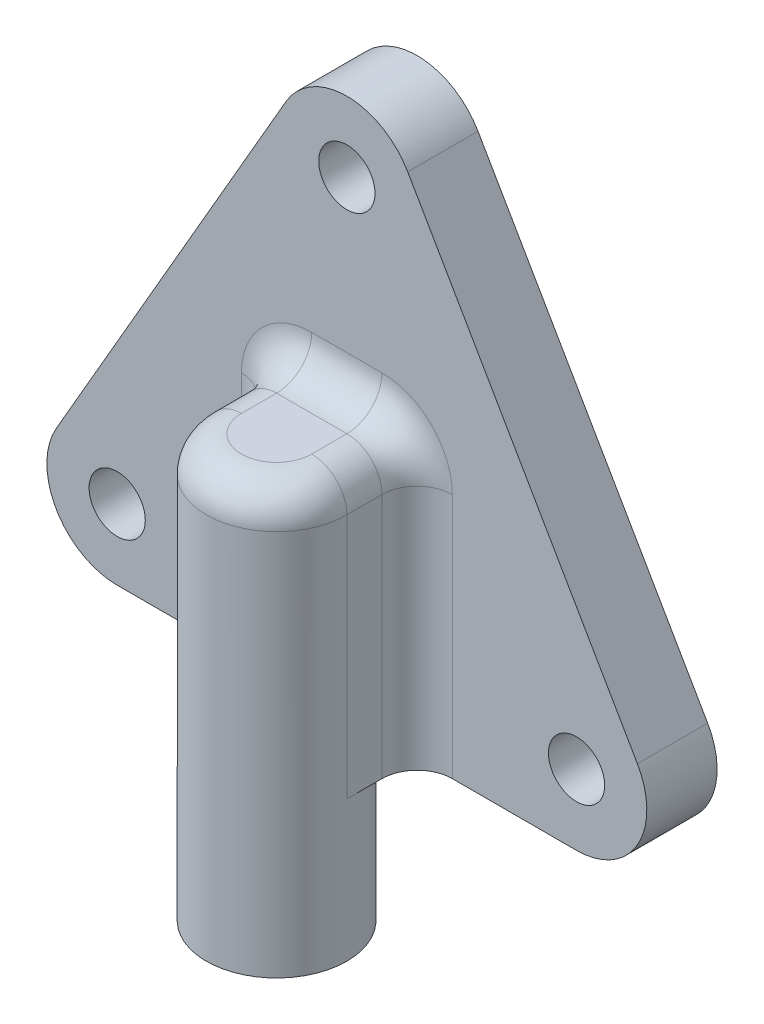
SolidWorks part; units mm, degrees
note: The reader was unsure of these and kept them because the rebuilt part matched: shared geometry of "Schizzo2<3>".
ref_plane "Piano frontale" through (0, 0, 0) normal (0, 0, 1) x (1, 0, 0)
ref_plane "Piano superiore" through (0, 0, 0) normal (0, 1, 0) x (1, 0, 0)
ref_plane "Piano destro" through (0, 0, 0) normal (1, 0, 0) x (0, 0, -1)
sketch "Schizzo1" plane through (0, 0, 0) normal (0, 0, 1) x (1, 0, 0)
  line L1 (41.3397, -13.8675) -> (8.6603, 42.735)
  line L2 (-8.6603, 42.735) -> (-41.3397, -13.8675)
  line L3 (-32.6795, -28.8675) -> (32.6795, -28.8675)
  circle A0 centre (0, 0) radius 28.8675 construction
  arc A1 (-41.3397, -13.8675) -> (-32.6795, -28.8675) centre (-32.6795, -18.8675) ccw
  arc A2 (41.3397, -13.8675) -> (32.6795, -28.8675) centre (32.6795, -18.8675) cw
  arc A3 (8.6603, 42.735) -> (-8.6603, 42.735) centre (0, 37.735) ccw
  point P8 (-50, -28.8675)
  point P11 (50, -28.8675)
  dimension "D2" = 10
  dimension "D1" = 100
extrude "Estrusione-Estrusione1" add sketch "Schizzo1" along normal blind 10
sketch "Schizzo2" plane through (0, -28.8675, 0) normal (0, -1, 0) x (1, 0, 0)
  line L0 (-10, 20) -> (-10, 10)
  line L1 (-10, 10) -> (10, 10)
  line L2 (10, 10) -> (10, 20)
  line L3 (-32.6795, 10) -> (32.6795, 10) construction
  line L5 (0, 0) -> (0, 20) construction
  line L6 (-32.6795, 0) -> (32.6795, 0) construction
  circle A1 centre (0, 20) radius 10
  point P4 (-6.2889, 20)
  dimension "D1" = 20
extrude "Estrusione-Estrusione2" add sketch "Schizzo2" against normal blind 40
extrude "Estrusione-Estrusione3" add sketch "Schizzo2<3>" along normal blind 20
sketch "Schizzo2<3>" plane through (0, -28.8675, 0) normal (0, -1, 0) x (1, 0, 0) same geometry as "Schizzo2"
hole_wizard "Foro Ø10.0 (10)-1" positions "Schizzo5" profile "Schizzo7" hole size "Ø10.0" standard "ISO"
sketch "Schizzo5" plane through (0, -48.8675, 0) normal (0, -1, 0) x (-1, 0, 0)
  circle A0 centre (0, -20) radius 10 construction
  point P5 (0, -20)
  point P8 (0, 0)
sketch "Schizzo7" plane through (0, -48.8675, 20) normal (1, 0, 0) x (0, 0, -1)
  line L0 (0, 0) -> (0, 45)
  line L1 (0, 45) -> (5, 45)
  line L2 (5, 45) -> (5, 0)
  line L5 (5, 0) -> (0, 0)
  line L10 (0, 45) -> (-5, 45) construction
  line L11 (0, -6.35) -> (0, 107.95) construction
  dimension "Hole Dia." = 10
  dimension "Hole Depth" = 45
  dimension "Drill Angle" = 180
hole_wizard "Foro Ø8.0 (8)-1" positions "Schizzo8" profile "Schizzo9" hole size "Ø8.0" standard "ISO" end condition through all
sketch "Schizzo8" plane through (0, 0, 10) normal (0, 0, 1) x (1, 0, 0)
  point P0 (0, 37.735)
  point P3 (-32.6795, -18.8675)
  point P6 (32.6795, -18.8675)
sketch "Schizzo9" plane through (0, 37.735, 10) normal (1, 0, 0) x (0, -1, 0)
  line L0 (0, 0) -> (0, 10)
  line L1 (0, 10) -> (4, 10)
  line L2 (4, 10) -> (4, 0)
  line L5 (4, 0) -> (0, 0)
  line L11 (0, -6.35) -> (0, 107.95) construction
  dimension "Thru Hole Dia." = 8
  dimension "Thru Hole Depth" = 10
fillet "Raccordo1" radius 5 3 edges at (10, 11.1325, 15) (-10, 11.1325, 15) (0, 11.1325, 30)
fillet "Raccordo2" radius 5 5 edges at (10, -11.3675, 10) (8.5355, 9.668, 10) (0, 11.1325, 10) (-8.5355, 9.668, 10) (-10, -11.3675, 10)
